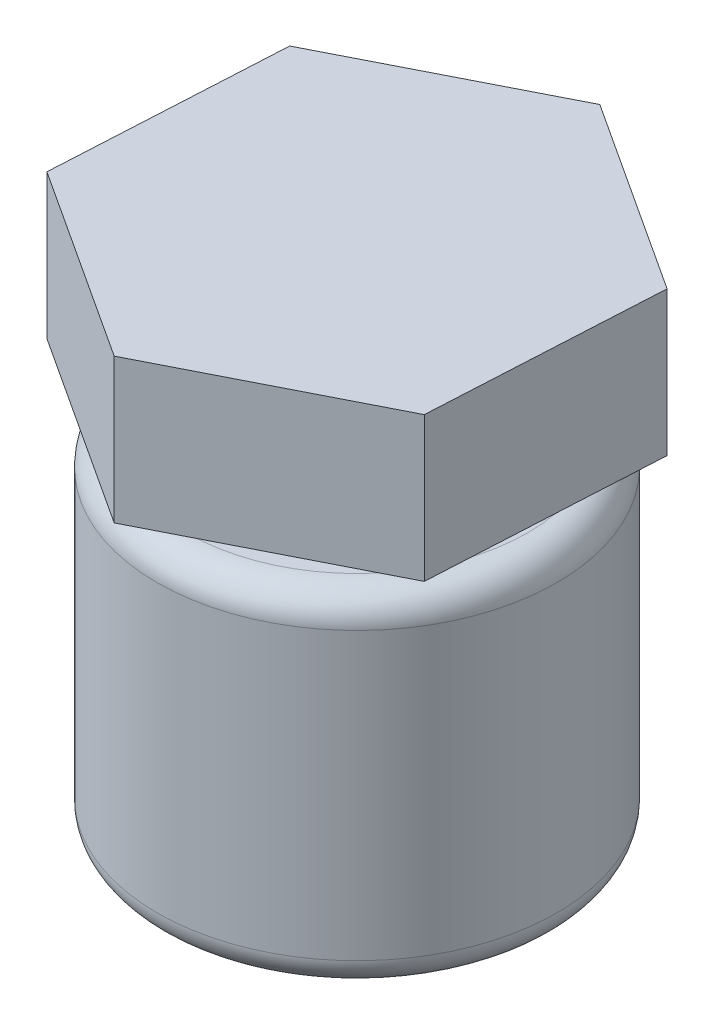
SolidWorks part; units mm, degrees
ref_plane "Front Plane" through (0, 0, 0) normal (0, 0, 1) x (1, 0, 0)
ref_plane "Top Plane" through (0, 0, 0) normal (0, 1, 0) x (1, 0, 0)
ref_plane "Right Plane" through (0, 0, 0) normal (1, 0, 0) x (0, 0, -1)
sketch "Sketch1" plane through (0, 0, 0) normal (0, 0, 1) x (1, 0, 0)
  line L0 (0, 55.1606) -> (6.0583, 55.1606)
  line L1 (6.0583, 55.1606) -> (6.0583, 45.3911)
  line L2 (6.0583, 45.3911) -> (11.4938, 45.3911)
  line L3 (11.4938, 45.3911) -> (11.4938, 33.6873)
  line L4 (11.4938, 33.6873) -> (12.618, 33.6873)
  line L5 (12.618, 33.6873) -> (12.618, 32.5135)
  line L6 (12.618, 32.5135) -> (11.4938, 32.5135)
  line L7 (11.4938, 32.5135) -> (11.4938, 22.622)
  line L8 (11.4938, 22.622) -> (69.149, 22.622)
  line L9 (69.149, 22.622) -> (69.149, -96.3702)
  line L10 (69.149, -96.3702) -> (0, -96.3702)
  line L11 (0, -96.3702) -> (0, -81.7)
  line L12 (0, -81.7) -> (63.1287, -81.7)
  line L13 (63.1287, -81.7) -> (63.1287, 18.3583)
  line L14 (63.1287, 18.3583) -> (5.3516, 18.3583)
  line L15 (5.3516, 18.3583) -> (0, 18.3583)
  line L16 (0, 18.3583) -> (0, 55.1606)
  point P17 (0, 0)
  point P19 (11.4938, 22.622)
  point P20 (15.3613, 35.7219)
  point P21 (10.7666, 45.3911)
  point P22 (11.4938, 35.7219)
  point P23 (6.0583, 55.1606)
  point P24 (12.618, 32.5135)
revolve "Revolve1" add sketch "Sketch1" angle 360 about L16
fillet "Fillet1" radius 10 1 edges at (0, 22.622, -69.149)
fillet "Fillet2" radius 10 1 edges at (0, -96.3702, -69.149)
sketch "Sketch2" plane through (0, 33.6873, 0) normal (0, 1, 0) x (1, 0, 0)
  line L1 (71.2052, 36.1284) -> (4.3145, 79.7297)
  line L2 (4.3145, 79.7297) -> (-66.8907, 43.6013)
  line L3 (-66.8907, 43.6013) -> (-71.2052, -36.1284)
  line L4 (-71.2052, -36.1284) -> (-4.3145, -79.7297)
  line L5 (-4.3145, -79.7297) -> (66.8907, -43.6013)
  line L6 (66.8907, -43.6013) -> (71.2052, 36.1284)
  circle A0 centre (0, 0) radius 69.149 construction
  circle A3 centre (0, 0) radius 69.149 construction
extrude "Boss-Extrude1" add sketch "Sketch2" along normal blind 50 separate body
revolve "Cut-Revolve1" cut sketch "Sketch1<3>" angle 360 about L16
sketch "Sketch1<3>" plane through (0, 0, 0) normal (0, 0, 1) x (1, 0, 0) same geometry as "Sketch1"
